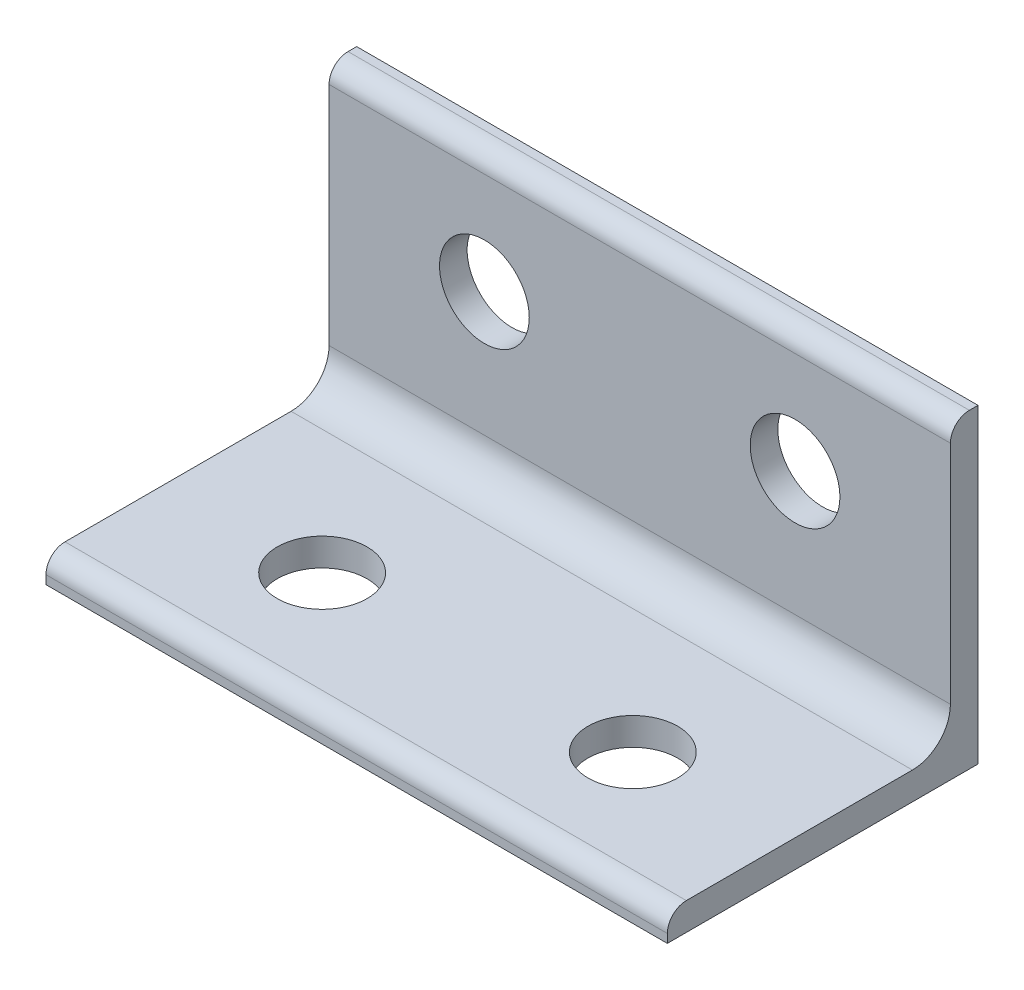
SolidWorks part; units mm, degrees
note: '?' marks a value the reader was unsure of.
other "Connection Feature"
ref_plane "Front Plane" through (0, 0, 0) normal (0, 0, 1) x (1, 0, 0)
ref_plane "Top Plane" through (0, 0, 0) normal (0, 1, 0) x (1, 0, 0)
ref_plane "Right Plane" through (0, 0, 0) normal (1, 0, 0) x (0, 0, -1)
ref_axis "Axis1" through (-18.99, 0, 0) along (1, 0, 0)?
sketch "Sketch1" plane through (0, 0, 0) normal (0, 0, 1) x (1, 0, 0)
  line L0 (0, 0) -> (180, 0)
  dimension "D1" = 180
other "Angles equal 90 X 90 X 8(1)" corner treatment miter
ref_plane "Plane1" through (0, 45, 45) normal (1, 0, 0) x (0, 1, 0)
sketch "Sketch11" plane through (0, 45, 45) normal (1, 0, 0) x (0, 1, 0)
  line L0 (-45, 45) -> (-45, -45)
  line L1 (-45, -45) -> (45, -45) construction
  line L2 (-45, -45) -> (-45, 45) construction
  line L3 (-45, 45) -> (45, 45) construction
  line L4 (45, -45) -> (45, 45) construction
  line L5 (-45, -45) -> (45, 45) construction
  line L6 (-45, 45) -> (45, -45) construction
  line L7 (-45, -45) -> (45, -45)
  line L8 (45, -45) -> (45, -42.5)
  line L9 (39.5, -37) -> (-26, -37)
  line L10 (-37, -26) -> (-37, 39.5)
  line L11 (-42.5, 45) -> (-45, 45)
  arc A0 (-26, -37) -> (-37, -26) centre (-26, -26) cw
  arc A1 (-37, 39.5) -> (-42.5, 45) centre (-42.5, 39.5) ccw
  arc A2 (45, -42.5) -> (39.5, -37) centre (39.5, -42.5) ccw
  point P0 (0, 0)
  point P13 (-37, 45)
  point P16 (45, -37)
  point P17 (-45, 0)
  point P18 (-45, 45)
  point P19 (0, -45)
  point P20 (-45, -45)
  point P21 (0, 0)
  point P22 (45, -45)
  point P23 (45, 0)
  point P24 (45, 45)
  point P25 (0, 45)
  point P26 (0, 0)
  dimension "r1" = 11
  dimension "r2" = 5.5
  dimension "hxb" = 90
  dimension "t" = 8
sketch "Sketch12" plane through (0, 0, 0) normal (0, 1, 0) x (1, 0, 0)
  line L2 (0, -49.5) -> (0, 49.5) construction
  line L3 (-49.5, 0) -> (49.5, 0) construction
  circle A0 centre (45, -55) radius 13
  dimension "D1" = 26
  dimension "D2" = 45
  dimension "G Back Mark A" = 55
extrude "Cut-Extrude1" cut sketch "Sketch12" along normal through all both and the other way through all
pattern_linear "LPattern1" count 2 spacing 90 along (1, 0, 0) of "Cut-Extrude1"
sketch "Sketch13" plane through (0, 0, 8) normal (0, 0, 1) x (1, 0, 0)
  line L0 (49.5, 0) -> (-49.5, 0) construction
  line L1 (0, -49.5) -> (0, 49.5) construction
  circle A0 centre (45, 55) radius 13
  dimension "D1" = 26
  dimension "G Back Mark B" = 55
  dimension "D3" = 45
extrude "Cut-Extrude2" cut sketch "Sketch13" against normal up to next
pattern_linear "LPattern2" count 2 spacing 90 along (1, 0, 0) of "Cut-Extrude2"
equation "\"Length\"= ( \"Number of Holes\" - 1 ) * \"Hole Pitch\" + \"Hole End Distance\" * 2"
equation "\"Hole Dia\" = 26"
equation "\"Hole Pitch\" = 90"
equation "\"G Back Mark A\"= 55"
equation "\"Hole End Distance\" = 45"
equation "\"D1@Sketch12\"=\"Hole Dia\""
equation "\"D3@LPattern1\"= \"Hole Pitch\""
equation "\"Number of Holes\"= 2"
equation "\"D1@LPattern1\"= \"Number of Holes\""
equation "\"D2@Sketch12\"=\"Hole End Distance\""
equation "\"D1@Sketch1\"=\"Length\""
equation "\"D3@LPattern2\"= \"Hole Pitch\""
equation "\"D1@LPattern2\"= \"Number of Holes\""
equation "\"D3@Sketch13\"= \"Hole End Distance\""
equation "\"D1@Sketch13\"= \"Hole Dia\""
equation "\"G Back Mark B\"= 55"
